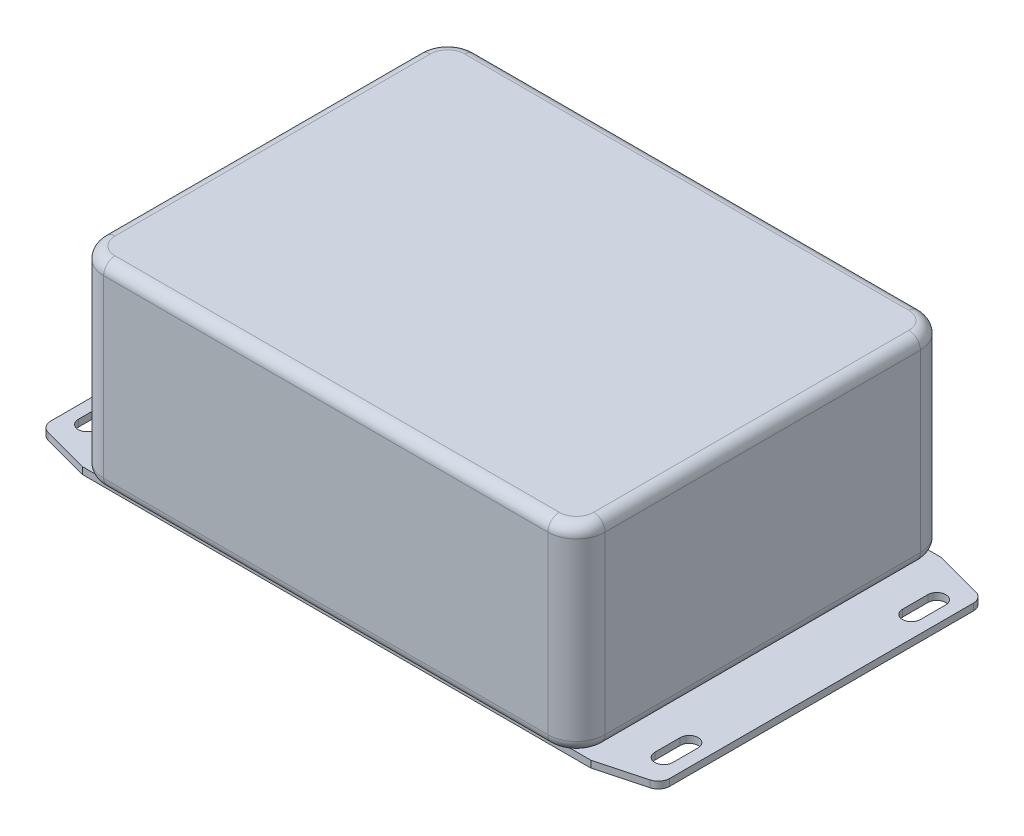
SolidWorks part; units mm, degrees
ref_plane "Front Plane" through (0, 0, 0) normal (0, 0, 1) x (1, 0, 0)
ref_plane "Top Plane" through (0, 0, 0) normal (0, 1, 0) x (1, 0, 0)
ref_plane "Right Plane" through (0, 0, 0) normal (1, 0, 0) x (0, 0, -1)
sketch "Sketch1" plane through (0, 0, 0) normal (0, 1, 0) x (1, 0, 0)
  line L0 (-63.881, 24.6253) -> (-63.881, 30.2387) construction
  line L1 (-63.881, -27.432) -> (63.881, -27.432) construction
  line L2 (-63.881, -27.432) -> (-63.881, 27.432) construction
  line L3 (-63.881, 27.432) -> (63.881, 27.432) construction
  line L4 (63.881, -27.432) -> (63.881, 27.432) construction
  line L5 (-63.881, -27.432) -> (63.881, 27.432) construction
  line L6 (-63.881, 27.432) -> (63.881, -27.432) construction
  line L7 (-65.8622, 24.6253) -> (-65.8622, 30.2387)
  line L8 (-61.8998, 24.6253) -> (-61.8998, 30.2387)
  line L9 (63.881, 24.6253) -> (63.881, 30.2387) construction
  line L12 (61.8998, 24.6253) -> (61.8998, 30.2387)
  line L15 (65.8622, 24.6253) -> (65.8622, 30.2387)
  line L18 (63.881, -30.2387) -> (63.881, -24.6253) construction
  line L19 (61.8998, -30.2387) -> (61.8998, -24.6253)
  line L20 (65.8622, -30.2387) -> (65.8622, -24.6253)
  line L21 (-63.881, -30.2387) -> (-63.881, -24.6253) construction
  line L22 (-65.8622, -30.2387) -> (-65.8622, -24.6253)
  line L23 (-61.8998, -30.2387) -> (-61.8998, -24.6253)
  line L24 (-68.58, 33.6291) -> (-68.58, -33.6291)
  line L25 (49.2125, -41.275) -> (-49.2125, -41.275) construction
  line L26 (55.5625, -34.925) -> (55.5625, 34.925) construction
  line L27 (49.2125, 41.275) -> (-49.2125, 41.275) construction
  line L28 (-55.5625, -34.925) -> (-55.5625, 34.925) construction
  line L29 (55.5625, -41.275) -> (-55.5625, 41.275) construction
  line L30 (55.5625, 41.275) -> (-55.5625, -41.275) construction
  line L31 (56.3245, 38.862) -> (66.6974, 36.0826)
  line L32 (68.58, 33.6291) -> (68.58, -33.6291)
  line L33 (68.58, 0) -> (0, 0) construction
  line L34 (0, 0) -> (0, 38.862) construction
  line L35 (0, 38.862) -> (56.3245, 38.862)
  line L36 (-56.3245, 38.862) -> (-66.6974, 36.0826)
  line L37 (0, 38.862) -> (-56.3245, 38.862)
  line L38 (-56.3245, -38.862) -> (-66.6974, -36.0826)
  line L39 (0, -38.862) -> (-56.3245, -38.862)
  line L40 (0, -38.862) -> (56.3245, -38.862)
  line L41 (56.3245, -38.862) -> (66.6974, -36.0826)
  arc A0 (-65.8622, 24.6253) -> (-61.8998, 24.6253) centre (-63.881, 24.6253) ccw
  arc A1 (-61.8998, 30.2387) -> (-65.8622, 30.2387) centre (-63.881, 30.2387) ccw
  arc A8 (61.8998, 24.6253) -> (65.8622, 24.6253) centre (63.881, 24.6253) ccw
  arc A9 (65.8622, 30.2387) -> (61.8998, 30.2387) centre (63.881, 30.2387) ccw
  arc A10 (61.8998, -30.2387) -> (65.8622, -30.2387) centre (63.881, -30.2387) ccw
  arc A11 (65.8622, -24.6253) -> (61.8998, -24.6253) centre (63.881, -24.6253) ccw
  arc A12 (-65.8622, -30.2387) -> (-61.8998, -30.2387) centre (-63.881, -30.2387) ccw
  arc A13 (-61.8998, -24.6253) -> (-65.8622, -24.6253) centre (-63.881, -24.6253) ccw
  arc A14 (-49.2125, -41.275) -> (-55.5625, -34.925) centre (-49.2125, -34.925) cw construction
  arc A15 (49.2125, -41.275) -> (55.5625, -34.925) centre (49.2125, -34.925) ccw construction
  arc A16 (55.5625, 34.925) -> (49.2125, 41.275) centre (49.2125, 34.925) ccw construction
  arc A17 (-49.2125, 41.275) -> (-55.5625, 34.925) centre (-49.2125, 34.925) ccw construction
  arc A18 (66.6974, 36.0826) -> (68.58, 33.6291) centre (66.04, 33.6291) cw
  arc A19 (-66.6974, 36.0826) -> (-68.58, 33.6291) centre (-66.04, 33.6291) ccw
  arc A20 (-66.6974, -36.0826) -> (-68.58, -33.6291) centre (-66.04, -33.6291) cw
  arc A21 (66.6974, -36.0826) -> (68.58, -33.6291) centre (66.04, -33.6291) ccw
  point P0 (0, 0)
  point P8 (-63.881, 27.432)
  point P17 (63.881, 27.432)
  point P24 (63.881, -27.432)
  point P31 (-63.881, -27.432)
  point P36 (0, 0)
  point P69 (-68.58, 0)
  point P72 (-66.7852, -35.8034)
  point P73 (-60.2573, -38.6113)
  point P74 (-66.6066, -35.5167)
  point P75 (-54.3682, -38.6483)
  point P76 (-66.6237, -36.5213)
  point P77 (-68.58, -34.0927)
  point P78 (-66.6681, -35.4117)
  dimension "D3" = 9.5758
  dimension "D9" = 6.35
  dimension "D10" = 137.16
  dimension "D13" = 2.54
  dimension "D1" = 54.864
  dimension "D2" = 127.762
  dimension "D4" = 3.9624
  dimension "D7" = 82.55
  dimension "D8" = 111.125
  dimension "D11" = 0.762
  dimension "D12" = 77.724
  dimension "D14" = 15
  dimension "D5" = 2
  dimension "D6" = 2
extrude "Boss-Extrude1" add sketch "Sketch1" along normal blind 1.524
sketch "Sketch2" plane through (0, 1.524, 0) normal (0, 1, 0) x (1, 0, 0)
  line L0 (55.5625, -34.925) -> (55.5625, 34.925) construction
  line L1 (49.2125, -41.275) -> (-49.2125, -41.275) construction
  line L2 (-55.5625, -34.925) -> (-55.5625, 34.925) construction
  line L3 (49.2125, 41.275) -> (-49.2125, 41.275) construction
  line L4 (55.5625, -34.925) -> (55.5625, 34.925)
  line L5 (49.2125, -41.275) -> (-49.2125, -41.275)
  line L6 (-55.5625, -34.925) -> (-55.5625, 34.925)
  line L7 (49.2125, 41.275) -> (-49.2125, 41.275)
  arc A0 (55.5625, 34.925) -> (49.2125, 41.275) centre (49.2125, 34.925) ccw construction
  arc A1 (49.2125, -41.275) -> (55.5625, -34.925) centre (49.2125, -34.925) ccw construction
  arc A2 (-55.5625, -34.925) -> (-49.2125, -41.275) centre (-49.2125, -34.925) ccw construction
  arc A3 (-49.2125, 41.275) -> (-55.5625, 34.925) centre (-49.2125, 34.925) ccw construction
  arc A4 (55.5625, 34.925) -> (49.2125, 41.275) centre (49.2125, 34.925) ccw
  arc A5 (49.2125, -41.275) -> (55.5625, -34.925) centre (49.2125, -34.925) ccw
  arc A6 (-55.5625, -34.925) -> (-49.2125, -41.275) centre (-49.2125, -34.925) ccw
  arc A7 (-49.2125, 41.275) -> (-55.5625, 34.925) centre (-49.2125, 34.925) ccw
extrude "Boss-Extrude2" add sketch "Sketch2" along normal offset from surface (43.942 mm away) 45.466 separate body up to face at (0, 0, 0)
fillet "Fillet1" radius 2.54 16 edges at (53.7026, 45.466, -39.4151) (55.5625, 45.466, 0) (53.7026, 45.466, 39.4151) (0, 45.466, 41.275) (-53.7026, 45.466, 39.4151) (-55.5625, 45.466, 0) (-53.7026, 45.466, -39.4151) (0, 45.466, -41.275) (0, 1.524, -41.275) (-53.7026, 1.524, -39.4151) (-55.5625, 1.524, 0) (-53.7026, 1.524, 39.4151) (0, 1.524, 41.275) (53.7026, 1.524, 39.4151) (55.5625, 1.524, 0) (53.7026, 1.524, -39.4151)
combine bodies "Combine1" operation type add bodies to combine 107 106
